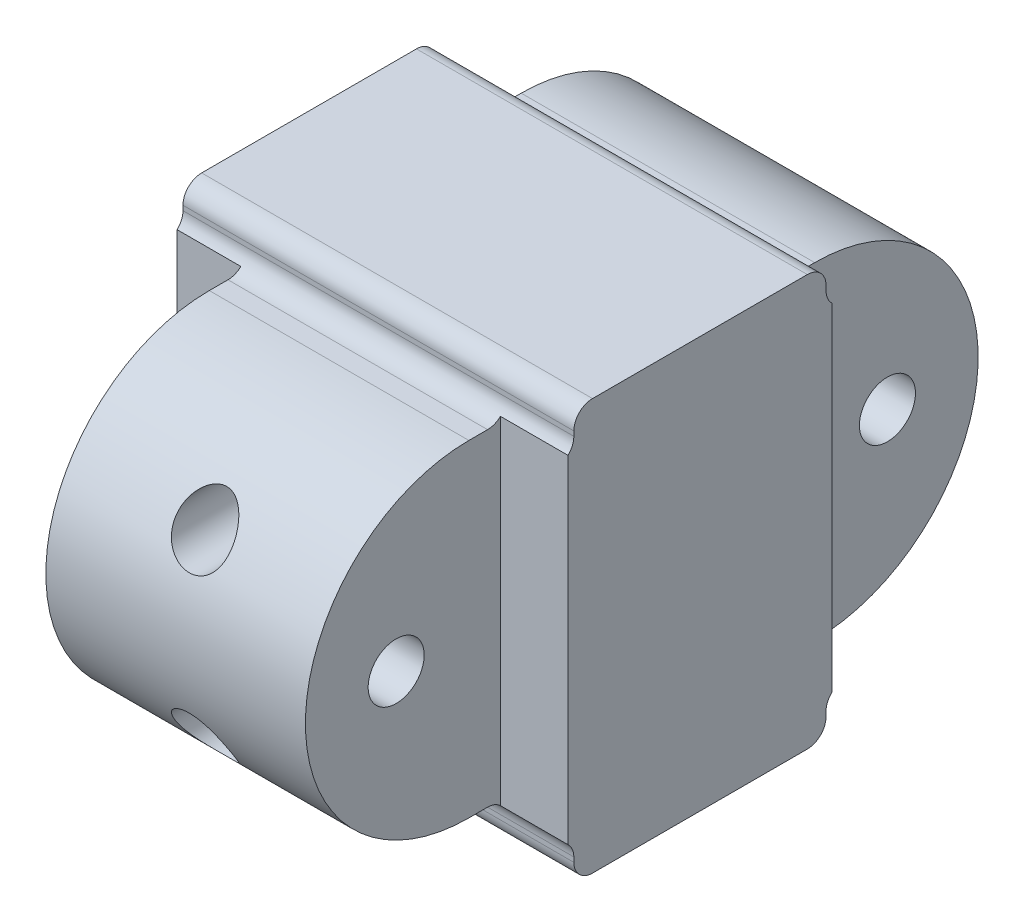
SolidWorks part; units mm, degrees
ref_plane "Front Plane" through (0, 0, 0) normal (0, 0, 1) x (1, 0, 0)
ref_plane "Top Plane" through (0, 0, 0) normal (0, 1, 0) x (1, 0, 0)
ref_plane "Right Plane" through (0, 0, 0) normal (1, 0, 0) x (0, 0, -1)
sketch3d "3DSketch1"
  line L2 (-19.9456, 27.4792, 53.8354) -> (0.9768, 27.4792, 53.8354)
  line L4 (-19.9456, 27.4792, 53.8354) -> (-19.9456, 5.4792, 53.8354)
  line L5 (-19.9456, 5.4792, 53.8354) -> (0.9768, 5.4792, 53.8354)
  line L6 (0.9768, 5.4792, 53.8354) -> (0.9768, 27.4792, 53.8354)
ref_plane "Plane1" through (0, 0, 53.8354) normal (0, 0, -1) x (-1, 0, 0)
sketch "Sketch2" plane through (0, 0, 53.8354) normal (0, 0, -1) x (-1, 0, 0)
  line L0 (19.9456, 27.4792) -> (19.9456, 5.4792)
  line L1 (19.9456, 5.4792) -> (-0.9768, 5.4792)
  line L2 (-0.9768, 5.4792) -> (-0.9768, 27.4792)
  line L3 (-0.9768, 27.4792) -> (19.9456, 27.4792)
extrude "Boss-Extrude1" add sketch "Sketch2" against normal blind 35
sketch "Sketch3" plane through (-19.9456, 0, 0) normal (-1, 0, 0) x (0, 0, 1)
  line L1 (88.8354, 27.4792) -> (53.8354, 27.4792) construction
  line L2 (88.8354, 5.4792) -> (53.8354, 5.4792) construction
  line L4 (88.8354, 5.4792) -> (88.8354, 27.4792) construction
  line L9 (71.3354, 27.4792) -> (71.3354, 5.4792) construction
  line L10 (62.5854, 25.2292) -> (62.5854, 27.4792)
  line L11 (62.5854, 7.7292) -> (62.5854, 5.4792)
  line L12 (53.8354, 16.4792) -> (58.6921, 16.4792) construction
  line L13 (80.0854, 27.4792) -> (80.0854, 16.4792) construction
  line L15 (71.3354, 27.4792) -> (71.3354, 5.4792) construction
  line L16 (71.3354, 5.4792) -> (88.8354, 5.4792) construction
  line L17 (88.8354, 27.4792) -> (88.8354, 5.4792) construction
  line L19 (80.0854, 25.2292) -> (80.0854, 27.4792)
  line L20 (80.0854, 7.7292) -> (80.0854, 5.4792)
  arc A1 (53.8354, 16.4792) -> (62.5854, 25.2292) centre (62.5854, 16.4792) cw
  arc A2 (53.8354, 16.4792) -> (62.5854, 7.7292) centre (62.5854, 16.4792) ccw
  circle A3 centre (58.6921, 16.4792) radius 1.5
  arc A4 (88.8354, 16.4792) -> (80.0854, 7.7292) centre (80.0854, 16.4792) cw
  arc A5 (88.8354, 16.4792) -> (80.0854, 25.2292) centre (80.0854, 16.4792) ccw
  circle A6 centre (83.9786, 16.4792) radius 1.5
  spline S0 degree 3 poles (62.5854, 5.4792) (55.5032, -7.5997) (27.6429, 16.7569) (54.8472, 35.9656) (62.5854, 27.4792) knots 0 0 0 0 0.523232 1 1 1 1
  spline S1 degree 3 poles (80.0854, 5.4792) (87.4399, -7.3101) (114.9239, 16.4819) (87.4008, 40.475) (80.0854, 27.4792) knots 0 0 0 0 0.498892 1 1 1 1
extrude "Cut-Extrude1" cut sketch "Sketch3" against normal blind 31
sketch "Sketch4" plane through (0.9768, 0, 0) normal (1, 0, 0) x (0, 0, -1)
  line L0 (-53.8354, 16.4792) -> (-58.6921, 16.4792)
  line L1 (-53.8354, 5.4792) -> (-53.8354, 27.4792) construction
sketch "Sketch7" plane through (-19.9456, 0, 0) normal (-1, 0, 0) x (0, 0, 1)
  line L0 (62.5854, 25.2292) -> (64.5854, 25.2292)
  line L1 (64.5854, 25.2292) -> (64.5854, 27.4792)
  line L2 (80.0854, 27.4792) -> (62.5854, 27.4792) construction
  line L3 (64.5854, 27.4792) -> (62.5854, 27.4792)
  line L4 (62.5854, 27.4792) -> (62.5854, 25.2292)
  line L5 (80.0854, 25.2292) -> (78.0854, 25.2292)
  line L6 (78.0854, 25.2292) -> (78.0854, 27.4792)
  line L7 (78.0854, 27.4792) -> (80.0854, 27.4792)
  line L8 (80.0854, 27.4792) -> (80.0854, 25.2292)
extrude "Cut-Extrude3" cut sketch "Sketch7" against normal blind 22
sketch "Sketch8" plane through (-19.9456, 0, 0) normal (-1, 0, 0) x (0, 0, 1)
  line L0 (62.5854, 5.4792) -> (64.5854, 5.4792)
  line L1 (80.0854, 5.4792) -> (62.5854, 5.4792) construction
  line L2 (62.5854, 5.4792) -> (62.5854, 7.7292)
  line L3 (62.5854, 7.7292) -> (64.5854, 7.7292)
  line L4 (64.5854, 7.7292) -> (64.5854, 5.4792)
  line L5 (78.0854, 5.4792) -> (80.0854, 5.4792)
  line L6 (80.0854, 5.4792) -> (80.0854, 7.7292)
  line L7 (80.0854, 7.7292) -> (78.0854, 7.7292)
  line L8 (78.0854, 7.7292) -> (78.0854, 5.4792)
extrude "Cut-Extrude4" cut sketch "Sketch8" against normal blind 22
ref_plane "Plane8" through (-19.9456, 25.2292, 64.5854) normal (0, 1, 0) x (1, 0, 0)
sketch "Sketch11" plane through (0, 0, 53.8354) normal (0, 0, -1) x (-1, 0, 0)
  line L0 (19.9456, 5.4792) -> (19.9456, 7.455) construction
  line L1 (19.9456, 27.4792) -> (19.9456, 5.4792) construction
  line L2 (9.4844, 22.7342) -> (9.4844, 27.4792) construction
  line L3 (-0.9768, 5.4792) -> (-0.9768, 27.4792) construction
  line L4 (-0.9768, 7.455) -> (-0.9768, 5.4792) construction
  line L5 (19.9456, 27.4792) -> (19.9456, 25.5035) construction
  line L6 (19.9456, 27.4792) -> (-0.9768, 27.4792) construction
  line L7 (-0.9768, 25.5035) -> (-0.9768, 27.4792) construction
  line L8 (19.9456, 7.455) -> (19.9456, 11.7292) construction
  line L9 (9.4844, 27.4792) -> (9.4844, 21.2342) construction
  line L11 (19.9456, 25.5035) -> (19.9456, 21.2342) construction
  line L13 (19.9456, 25.5035) -> (17.3396, 25.5035) construction
  line L14 (17.3396, 25.5035) -> (17.3396, 22.8975) construction
  line L15 (19.9456, 7.455) -> (17.3396, 7.455) construction
  line L16 (17.3396, 7.455) -> (17.3396, 10.061) construction
  line L17 (-0.9768, 7.455) -> (1.6293, 7.455) construction
  line L18 (1.6293, 7.455) -> (1.6293, 10.061) construction
  line L19 (-0.9768, 25.5035) -> (1.6293, 25.5035) construction
  line L20 (1.6293, 25.5035) -> (1.6293, 22.8975) construction
  line L22 (-0.9768, 25.5035) -> (1.6293, 25.5035)
  line L23 (-0.9768, 25.5035) -> (-0.9768, 7.455)
  line L24 (-0.9768, 7.455) -> (1.6293, 7.455)
  line L25 (1.6293, 25.5035) -> (1.6293, 7.455)
  line L26 (17.3396, 25.5035) -> (19.9456, 25.5035)
  line L27 (17.3396, 25.5035) -> (17.3396, 7.455)
  line L28 (17.3396, 7.455) -> (19.9456, 7.455)
  line L29 (19.9456, 25.5035) -> (19.9456, 7.455)
  circle A0 centre (9.4844, 11.7292) radius 1.5
  circle A1 centre (9.4844, 21.2342) radius 1.5
  point P23 (0, 0)
  point P35 (2.0097, 25.3945)
  point P36 (1.6293, 7.455)
extrude "Cut-Extrude5" cut sketch "Sketch11" against normal blind 36
fillet "Fillet2" radius 1 8 edges at (-9.4844, 25.2292, 78.0854) (-9.4844, 27.4792, 78.0854) (-9.4844, 27.4792, 64.5854) (-9.4844, 25.2292, 64.5854) (-9.4844, 7.7292, 64.5854) (-9.4844, 5.4792, 64.5854) (-9.4844, 5.4792, 78.0854) (-9.4844, 7.7292, 78.0854)
sketch "Sketch12" plane through (0, 25.5035, 0) normal (0, -1, 0) x (1, 0, 0)
  line L1 (-19.9456, 64.2733) -> (-17.3396, 64.2733)
  line L2 (-19.9456, 64.2733) -> (-19.9456, 78.3974)
  line L3 (-19.9456, 78.3974) -> (-17.3396, 78.3974)
  line L4 (-17.3396, 64.2733) -> (-17.3396, 78.3974)
  line L5 (-19.9456, 64.2733) -> (-17.3396, 78.3974) construction
  line L6 (-19.9456, 78.3974) -> (-17.3396, 64.2733) construction
  line L7 (0.9768, 78.3974) -> (-1.6293, 78.3974)
  line L8 (0.9768, 78.3974) -> (0.9768, 64.2733)
  line L9 (0.9768, 64.2733) -> (-1.6293, 64.2733)
  line L10 (-1.6293, 78.3974) -> (-1.6293, 64.2733)
  line L11 (0.9768, 78.3974) -> (-1.6293, 64.2733) construction
  line L12 (0.9768, 64.2733) -> (-1.6293, 78.3974) construction
  point P4 (-18.6426, 71.3354)
  point P11 (-0.3263, 71.3354)
extrude "Boss-Extrude2" add sketch "Sketch12" along normal up to surface (18.0485 mm away) up to face at (-18.6426, 7.455, 71.3354)
ref_plane "Plane9" through (0, 0, 93.8354) normal (0, 0, -1) x (-1, 0, 0)
sketch "Sketch13" plane through (0, 0, 93.8354) normal (0, 0, -1) x (-1, 0, 0)
  line L1 (19.8464, 6.9826) -> (16.5367, 6.9826)
  line L2 (19.8464, 6.9826) -> (19.8464, 26.4417)
  line L3 (19.8464, 26.4417) -> (16.5367, 26.4417)
  line L4 (16.5367, 6.9826) -> (16.5367, 26.4417)
  line L5 (19.8464, 6.9826) -> (16.5367, 26.4417) construction
  line L6 (19.8464, 26.4417) -> (16.5367, 6.9826) construction
  line L7 (-0.609, 26.1547) -> (2.6409, 26.1547)
  line L8 (-0.609, 26.1547) -> (-0.609, 7.0312)
  line L9 (-0.609, 7.0312) -> (2.6409, 7.0312)
  line L10 (2.6409, 26.1547) -> (2.6409, 7.0312)
  line L11 (-0.609, 26.1547) -> (2.6409, 7.0312) construction
  line L12 (-0.609, 7.0312) -> (2.6409, 26.1547) construction
  point P4 (18.1916, 16.7121)
  point P9 (1.0159, 16.593)
  point P10 (16.7333, 6.9826)
  point P11 (2.1911, 26.1905)
  point P12 (16.5367, 26.4417)
  point P13 (2.6409, 26.1547)
extrude "Cut-Extrude6" cut sketch "Sketch13" along normal up to surface (15.438 mm away) up to face at (-0.3263, 16.4792, 78.3974)
